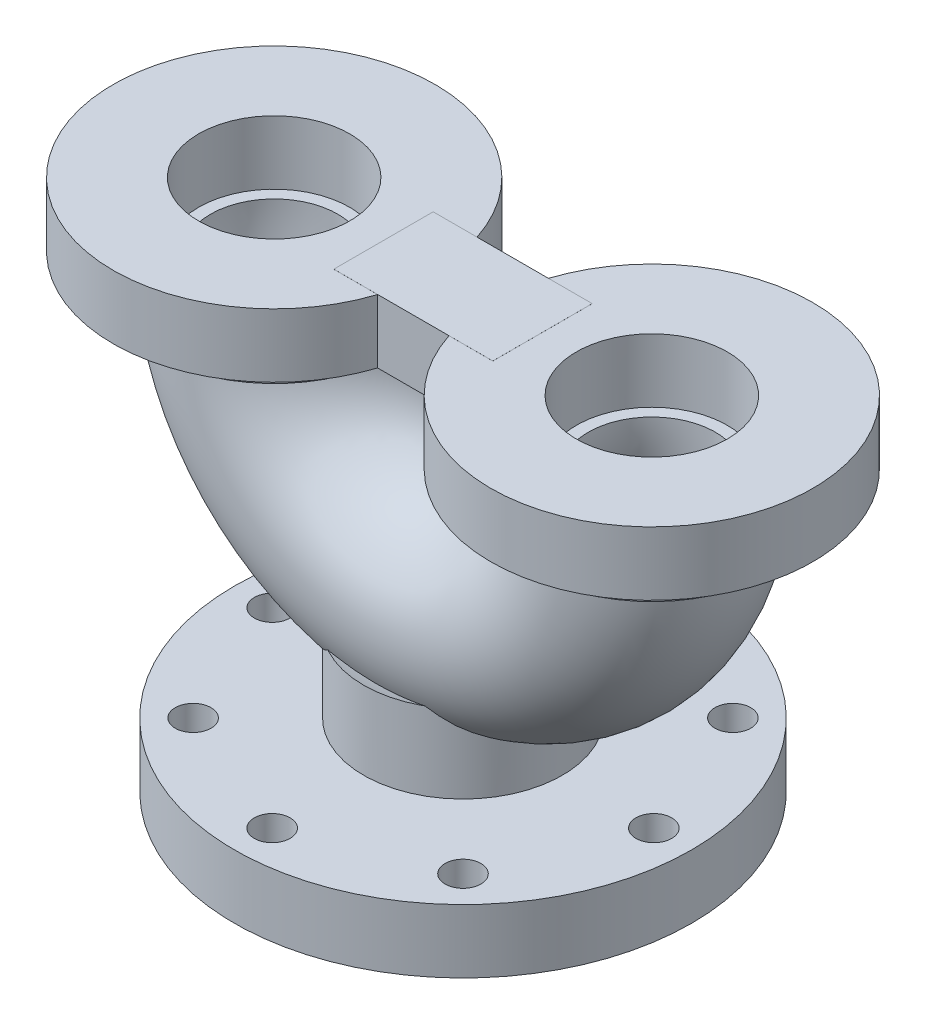
SolidWorks part; units mm, degrees
ref_plane "Front Plane" through (0, 0, 0) normal (0, 0, 1) x (1, 0, 0)
ref_plane "Top Plane" through (0, 0, 0) normal (0, 1, 0) x (1, 0, 0)
ref_plane "Right Plane" through (0, 0, 0) normal (1, 0, 0) x (0, 0, -1)
sketch "Sketch1" plane through (0, 0, 0) normal (0, 0, 1) x (1, 0, 0)
  line L0 (0, -103.1532) -> (0, 103.1532) construction
  line L1 (-63, 0) -> (-45, 0)
  line L2 (45, 0) -> (63, 0)
  line L3 (-145, 0) -> (-127, 0)
  line L4 (127, 0) -> (145, 0)
  arc A0 (45, 0) -> (-45, 0) centre (0, 0) cw
  arc A1 (63, 0) -> (-63, 0) centre (0, 0) cw
  arc A2 (127, 0) -> (-127, 0) centre (0, 0) cw
  arc A3 (145, 0) -> (-145, 0) centre (0, 0) cw
  point P5 (0, 0)
  point P17 (0, 0)
  point P18 (0, 0)
  dimension "D1" = 45
  dimension "D2" = 63
  dimension "D3" = 127
  dimension "D4" = 145
sketch "Sketch2" plane through (0, 0, 0) normal (0, 1, 0) x (1, 0, 0)
  line L0 (-145, 0) -> (145, 0) construction
  circle A0 centre (95, 0) radius 32
  circle A1 centre (95, 0) radius 50
  dimension "D1" = 18
sweep "Sweep1" add profiles "Sketch2" path "Sketch1"
sketch "Sketch3" plane through (0, 0, 0) normal (0, 0, 1) x (1, 0, 0)
  line L0 (0, 0) -> (0, -258.6735) construction
  line L1 (-50, -156) -> (-50, -116.7433)
  line L2 (115, -188) -> (-115, -188)
  line L3 (115, -188) -> (115, -156)
  line L4 (115, -156) -> (-115, -156)
  line L5 (-115, -188) -> (-115, -156)
  line L6 (115, -188) -> (-115, -156) construction
  line L7 (115, -156) -> (-115, -188) construction
  line L8 (-32, -156) -> (-32, -141.4249)
  line L9 (32, -156) -> (32, -141.4249)
  line L11 (50, -156) -> (50, -116.7433)
  line L12 (0, -127) -> (0, -156)
  line L13 (0, -156) -> (0, -188)
  arc A0 (-32, -141.4249) -> (32, -141.4249) centre (0, 0) ccw
  arc A1 (-50, -116.7433) -> (50, -116.7433) centre (0, 0) ccw
  point P3 (-49.998, -106.619)
  point P7 (0, -172)
  point P12 (-0.0011, -117.76)
  dimension "D5" = 127
  dimension "D1" = 32
  dimension "D2" = 188
  dimension "D3" = 230
  dimension "D4" = 100
  dimension "D6" = 18
revolve "Revolve1" add sketch "Sketch3" angle 360 about L0 region at (29.3347, -136.4429, 0)
revolve "Revolve2" add sketch "Sketch3<6>" angle 360 about L0 region at (57.5, -172, 0)
sketch "Sketch3<6>" plane through (0, 0, 0) normal (0, 0, 1) x (1, 0, 0) same geometry as "Sketch3"
sketch "Sketch6" plane through (0, -156, 0) normal (0, 1, 0) x (1, 0, 0)
  circle A0 centre (0, 0) radius 96 construction
  circle A1 centre (0, 0) radius 115 construction
  circle A2 centre (0, 96) radius 9
  circle A3 centre (67.8823, 67.8823) radius 9
  circle A4 centre (96, 0) radius 9
  circle A5 centre (67.8823, -67.8823) radius 9
  circle A6 centre (0, -96) radius 9
  circle A7 centre (-67.8823, -67.8823) radius 9
  circle A8 centre (-96, 0) radius 9
  circle A9 centre (-67.8823, 67.8823) radius 9
  point P8 (0, 0)
  point P23 (0, 0)
  dimension "D1" = 19
  dimension "D2" = 18
  dimension "D3" = 8
extrude "Cut-Extrude3" cut sketch "Sketch6" against normal through all
sketch "Sketch7" plane through (0, 0, 0) normal (0, 1, 0) x (1, 0, 0)
  line L0 (-176, 0) -> (176, 0) construction
  line L1 (0, 144.9907) -> (0, -144.9907) construction
  circle A1 centre (-95, 0) radius 81
  circle A4 centre (-95, 0) radius 38
  circle A5 centre (-95, 0) radius 32 construction
  circle A6 centre (95, 0) radius 38
  circle A7 centre (95, 0) radius 81
  point P9 (0, 0)
  point P15 (0, 0)
  dimension "D2" = 76
  dimension "D1" = 176
extrude "Boss-Extrude1" add sketch "Sketch7" along normal blind 32
sketch "Sketch9" plane through (0, 0, 0) normal (0, 1, 0) x (1, 0, 0)
  line L0 (0, 0) -> (0, -68.9225) construction
  circle A1 centre (-95, 0) radius 50
  circle A4 centre (-95, 0) radius 32 construction
  circle A5 centre (-95, 0) radius 62
  circle A6 centre (95, 0) radius 50
  circle A7 centre (95, 0) radius 62
  dimension "D1" = 100
  dimension "D2" = 12
extrude "Boss-Extrude2" add sketch "Sketch9" against normal blind 14
sketch "Sketch10" plane through (0, 32, 0) normal (0, 1, 0) x (1, 0, 0)
  line L1 (-40, -25) -> (40, -25)
  line L2 (-40, -25) -> (-40, 25)
  line L3 (-40, 25) -> (40, 25)
  line L4 (40, -25) -> (40, 25)
  line L5 (-40, -25) -> (40, 25) construction
  line L6 (-40, 25) -> (40, -25) construction
  point P0 (0, 0)
  dimension "D1" = 80
  dimension "D2" = 50
extrude "Boss-Extrude3" add sketch "Sketch10" against normal up to surface (32 mm away) up to face at (-157, 0, 0)
extrude "Boss-Extrude4" add sketch "Sketch10<2>" along normal blind 0.02
sketch "Sketch10<2>" plane through (0, 32, 0) normal (0, 1, 0) x (1, 0, 0) same geometry as "Sketch10"
